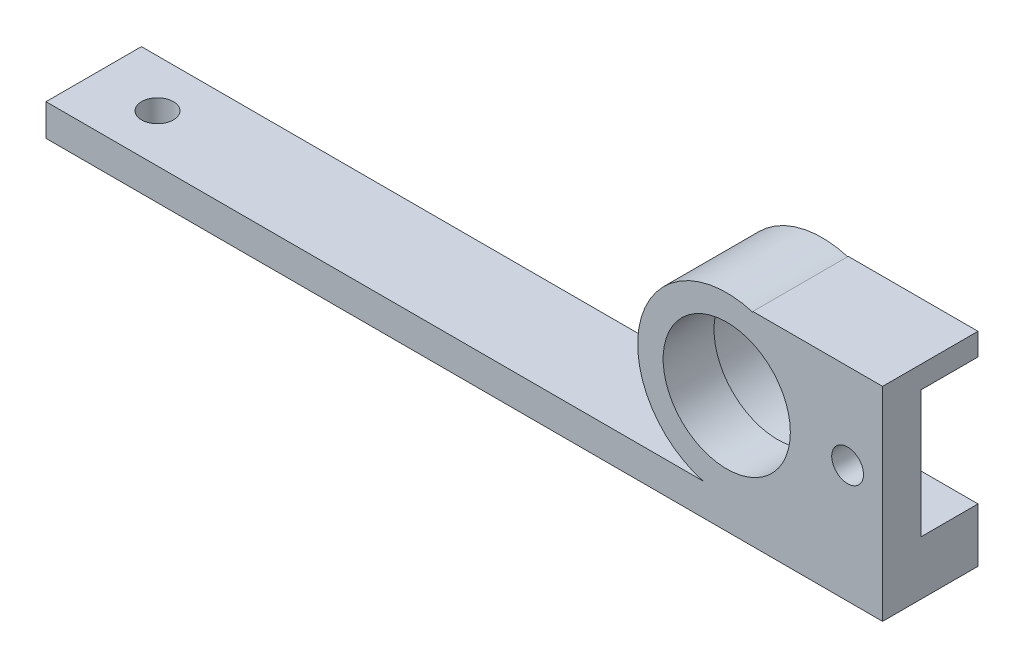
SolidWorks part; units mm, degrees
ref_plane "前视基准面" through (0, 0, 0) normal (0, 0, 1) x (1, 0, 0)
ref_plane "上视基准面" through (0, 0, 0) normal (0, 1, 0) x (1, 0, 0)
ref_plane "右视基准面" through (0, 0, 0) normal (1, 0, 0) x (0, 0, -1)
sketch "草图1" plane through (0, 0, 0) normal (0, 0, 1) x (1, 0, 0)
  line L1 (20, -10) -> (-20, -10)
  line L2 (20, -10) -> (20, 10)
  line L3 (20, 10) -> (-20, 10)
  line L4 (-20, -10) -> (-20, 10)
  line L5 (20, -10) -> (-20, 10) construction
  line L6 (20, 10) -> (-20, -10) construction
  point P0 (0, 0)
  dimension "D1" = 40
  dimension "D2" = 20
extrude "凸台-拉伸1" add sketch "草图1" along normal blind 6
sketch "草图2" plane through (0, 0, 6) normal (0, 0, 1) x (1, 0, 0)
  line L0 (20, -10) -> (20, 10) construction
  circle A0 centre (10, 0) radius 2.5
  circle A1 centre (-1, 0) radius 2.5
  circle A2 centre (-12, 0) radius 2.5
  dimension "D1" = 10
  dimension "D2" = 5
  dimension "D3" = 3
extrude "切除-拉伸1" cut sketch "草图2" against normal through all
sketch "草图3" plane through (0, 0, 6) normal (0, 0, 1) x (1, 0, 0)
  line L0 (20, 13.5) -> (20, 10)
  line L1 (20, -13.5) -> (-26.894, -13.5)
  line L3 (20, 13.5) -> (-26.894, 13.5)
  line L4 (-20, 10) -> (-20, -10)
  line L5 (-20, -10) -> (20, -10)
  line L6 (20, -10) -> (20, 10)
  line L7 (20, 10) -> (-20, 10)
  line L8 (-20, 10) -> (-20, -10)
  line L9 (-20, -10) -> (20, -10)
  line L10 (20, -10) -> (20, 10)
  line L11 (20, 10) -> (-20, 10)
  line L12 (-26.894, -13.5) -> (-26.894, 13.5)
  line L13 (20, -10.0394) -> (-26.894, 13.5) construction
  line L14 (20, 10.0394) -> (-26.894, -13.5) construction
  line L15 (20, -10) -> (20, -13.5)
  circle A0 centre (-31, 0) radius 11
  circle A1 centre (-31, 0) radius 14
  point P2 (0, 0)
  line M10 (-20, 10) -> (-20, -10)
  line M11 (-20, -10) -> (20, -10)
  line M13 (20, 10) -> (-20, 10)
  dimension "D3" = 22
  dimension "D4" = 28
  dimension "D2" = 3.5
  dimension "D1" = 0
extrude "凸台-拉伸2" add sketch "草图3" against normal blind 15 contours L3 A1 L1 L12 A0 | A1 L1 L15 M11 M10 | L1 A1 L8 A0 L12 | L8 A1 L3 L12 A0 | L8 A1 | A1 L0 L3 M10 M13 region at (-1.9449, 11.7771, 6) region at (-1.9449, -11.7771, 6) region at (-23.0173, 9.0328, 6) region at (-27.2274, 11.7946, 6) region at (-18.7882, 0, 6) region at (-23.0173, -9.0328, 6)
sketch "草图5" plane through (0, 0, 6) normal (0, 0, 1) x (1, 0, 0)
  circle A0 centre (-31, 0) radius 10
  circle A1 centre (-31, 0) radius 11 construction
  circle A2 centre (-31, 0) radius 11
  dimension "D1" = 20
extrude "凸台-拉伸3" add sketch "草图5" against normal blind 8
sketch "草图6" plane through (0, 0, 6) normal (0, 0, 1) x (1, 0, 0)
  circle A0 centre (-31, 0) radius 8.5
  circle A1 centre (-31, 0) radius 10 construction
  circle A2 centre (-31, 0) radius 10
  dimension "D1" = 17
sketch "草图8" plane through (0, 0, 6) normal (0, 0, 1) x (1, 0, 0)
  line L0 (20, -13.5) -> (20, 13.5) construction
  line L1 (20, -13.5) -> (-26.894, -13.5) construction
  line L2 (20, 13.5) -> (-26.894, 13.5) construction
  line L3 (20, -13.5) -> (20, 13.5)
  line L4 (20, -13.5) -> (-26.894, -13.5)
  line L5 (20, 13.5) -> (-26.894, 13.5)
  line L6 (-45, -14) -> (-26.894, -13.5)
  line L7 (-45, -14) -> (-239, -14)
  line L8 (-45, -14) -> (-45, 14)
  line L9 (-45, 14) -> (-239, 14)
  line L10 (-239, -14) -> (-239, 14)
  line L11 (-45, -14) -> (-239, 14) construction
  line L12 (-45, 14) -> (-239, -14) construction
  line L13 (-45, 14) -> (-26.894, 13.3843)
  line L14 (-12, 0) -> (-31, 0)
  arc A0 (-26.894, 13.3843) -> (-26.894, -13.3843) centre (-31, 0) ccw construction
  arc A1 (-26.894, 13.3843) -> (-26.894, -13.3843) centre (-31, 0) ccw
  point P6 (-142, 0)
  dimension "D1" = 28
  dimension "D2" = 194
  dimension "D3" = 14
sketch "草图9" plane through (0, -13.5, 0) normal (0, -1, 0) x (1, 0, 0)
  circle A0 centre (10.5344, 0) radius 5.2388
sketch "草图10" plane through (20, 0, 0) normal (1, 0, 0) x (0, 0, -1)
  line L1 (9, -13.5) -> (-6, -13.5)
  line L2 (9, -13.5) -> (9, -18.5)
  line L3 (9, -18.5) -> (-6, -18.5)
  line L4 (-6, -13.5) -> (-6, -18.5)
  dimension "D1" = 5
extrude "凸台-拉伸4" add sketch "草图10" against normal blind 500
sketch "草图11" plane through (0, 0, -9) normal (0, 0, -1) x (-1, 0, 0)
  line L1 (22.0371, -11.3638) -> (33.5283, -11.3638)
  line L2 (22.0371, -11.3638) -> (22.0371, -16.4864)
  line L3 (22.0371, -16.4864) -> (33.5283, -16.4864)
  line L4 (33.5283, -11.3638) -> (33.5283, -16.4864)
extrude "凸台-拉伸5" add sketch "草图11" against normal through all
sketch "草图12" plane through (0, 0, 6) normal (0, 0, 1) x (1, 0, 0)
  line L0 (-12, 0) -> (-1, 0) construction
  line L1 (-6.5, 0) -> (-6.5, 13.5) construction
  line L2 (20, 13.5) -> (-26.894, 13.5) construction
  line L4 (-6.5, 13.5) -> (20, 13.5)
  line L5 (-6.5, 13.5) -> (-6.5, -18.5)
  line L6 (-6.5, -18.5) -> (20, -18.5)
  line L7 (20, 13.5) -> (20, -18.5)
extrude "切除-拉伸2" cut sketch "草图12" against normal through all
sketch "草图13" plane through (0, -18.5, 0) normal (0, -1, 0) x (1, 0, 0)
  line L0 (-138.0156, 6) -> (-138.0156, -9.0491)
  line L1 (-480, 6) -> (-6.5, 6) construction
  line L2 (-138.0156, 140.8283) -> (-138.0156, -229.1717) construction
sketch "草图14" plane through (0, -18.5, 0) normal (0, -1, 0) x (1, 0, 0)
  line L1 (-138.0156, -9.0491) -> (-494.0275, -9.0491)
  line L2 (-138.0156, -9.0491) -> (-138.0156, 12.8124)
  line L3 (-138.0156, 12.8124) -> (-494.0275, 12.8124)
  line L4 (-494.0275, -9.0491) -> (-494.0275, 12.8124)
extrude "切除-拉伸3" cut sketch "草图14" against normal through all
sketch "草图15" plane through (0, -18.5, 0) normal (0, -1, 0) x (1, 0, 0)
  line L0 (-138.0156, -1.5245) -> (-128.0156, -1.5245) construction
  line L1 (-138.0156, 6) -> (-138.0156, -9.0491) construction
  circle A0 centre (-128.0156, -1.5245) radius 2.5
  dimension "D2" = 5
  dimension "D1" = 10
extrude "切除-拉伸4" cut sketch "草图15" against normal blind 10
